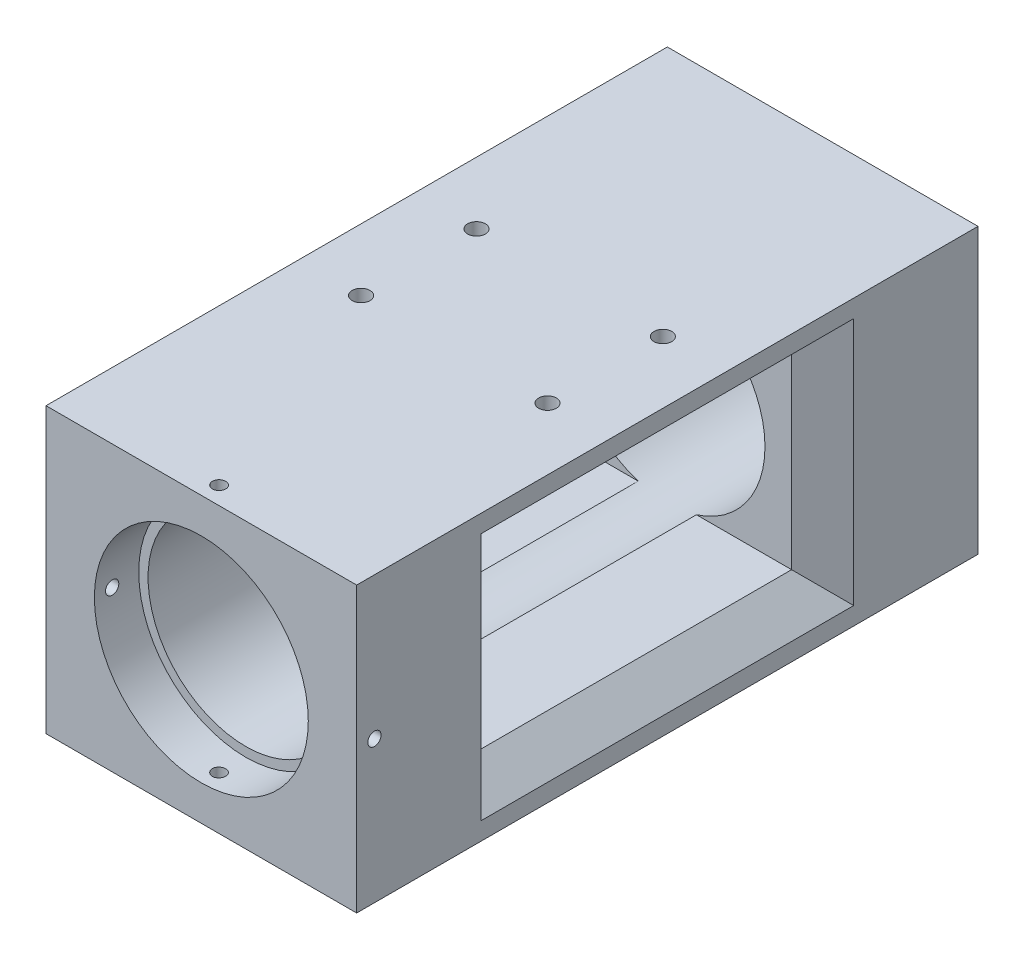
SolidWorks part; units mm, degrees
ref_plane "前视基准面" through (0, 0, 0) normal (0, 0, 1) x (1, 0, 0)
ref_plane "上视基准面" through (0, 0, 0) normal (0, 1, 0) x (1, 0, 0)
ref_plane "右视基准面" through (0, 0, 0) normal (1, 0, 0) x (0, 0, -1)
sketch "草图1" plane through (0, 0, 0) normal (0, 0, 1) x (1, 0, 0)
  line L1 (-35, -32) -> (35, -32)
  line L2 (-35, -32) -> (-35, 32)
  line L3 (-35, 32) -> (35, 32)
  line L4 (35, -32) -> (35, 32)
  line L5 (-35, -32) -> (35, 32) construction
  line L6 (-35, 32) -> (35, -32) construction
  point P0 (0, 0)
  dimension "D1" = 70
  dimension "D2" = 64
extrude "凸台-拉伸1" add sketch "草图1" along normal mid plane 140
sketch "草图2" plane through (0, 0, 70) normal (0, 0, 1) x (1, 0, 0)
  circle A0 centre (0, 0) radius 24.1
  dimension "D1" = 48.2
extrude "切除-拉伸1" cut sketch "草图2" against normal blind 10
sketch "草图3" plane through (0, 32, 0) normal (0, 1, 0) x (1, 0, 0)
  line L0 (35, -70) -> (-35, -70) construction
  circle A0 centre (0, -66) radius 1.5
  point P5 (0, -70)
  dimension "D1" = 3
  dimension "D2" = 4
extrude "切除-拉伸2" cut sketch "草图3" against normal through all
sketch "草图4" plane through (35, 0, 0) normal (1, 0, 0) x (0, 0, -1)
  line L0 (-70, -32) -> (-70, 32) construction
  circle A0 centre (-66, 0) radius 1.5
  point P4 (0, 0)
  dimension "D1" = 3
  dimension "D2" = 4
extrude "切除-拉伸3" cut sketch "草图4" against normal through all
sketch "草图5" plane through (0, 0, 60) normal (0, 0, 1) x (1, 0, 0)
  circle A0 centre (0, 0) radius 22
  dimension "D1" = 44
extrude "切除-拉伸4" cut sketch "草图5" against normal through all
sketch "草图6" plane through (35, 0, 0) normal (1, 0, 0) x (0, 0, -1)
  line L1 (-35, -21) -> (35, -21)
  line L2 (-35, -21) -> (-35, 21)
  line L3 (-35, 21) -> (35, 21)
  line L4 (35, -21) -> (35, 21)
  line L5 (-35, -21) -> (35, 21) construction
  line L6 (-35, 21) -> (35, -21) construction
  point P0 (0, 0)
  point P6 (0, 0)
  point P7 (-12.7908, 0.4915)
  point P9 (-18.5277, 0)
  point P10 (0, 0)
  dimension "D1" = 42
  dimension "D2" = 70
extrude "切除-拉伸5" cut sketch "草图6" against normal through all
chamfer "倒角1" distance 7 angle 45 8 edges at (-35, 0, -35) (-35, -21, 0) (-35, 0, 35) (-35, 21, 0) (35, 21, 0) (35, 0, -35) (35, 0, 35) (35, -21, 0)
sketch "草图7" plane through (0, 32, 0) normal (0, 1, 0) x (1, 0, 0)
  line L0 (-21, 13) -> (21, 13) construction
  circle A0 centre (-21, 13) radius 2
  circle A1 centre (21, 13) radius 2
  point P4 (0, 13)
  dimension "D1" = 4
  dimension "D2" = 42
  dimension "D3" = 13
extrude "切除-拉伸6" cut sketch "草图7" against normal blind 20
sketch "草图8" plane through (0, 21, 0) normal (0, -1, 0) x (1, 0, 0)
  circle A1 centre (21, -13) radius 2 construction
  circle A2 centre (21, -13) radius 5.5
  circle A3 centre (21, -13) radius 5.5
  circle A4 centre (21, -13) radius 2
  circle M2 centre (21, -13) radius 2
  dimension "D1" = 3.5
extrude "切除-拉伸7" cut sketch "草图8" against normal blind 7 contours A3 M2 region at (15.6556, 21, -13)
mirror "镜向1" about plane through (0, 0, 0) normal (1, 0, 0) of "切除-拉伸7"
mirror "镜向2" about plane through (0, 0, 0) normal (0, 0, 1) of "镜向1", "切除-拉伸7", "切除-拉伸6"
sketch "草图9" plane through (0, 0, 0) normal (1, 0, 0) x (0, 0, -1)
  line L0 (-112.2479, 0) -> (108.0194, 0)
